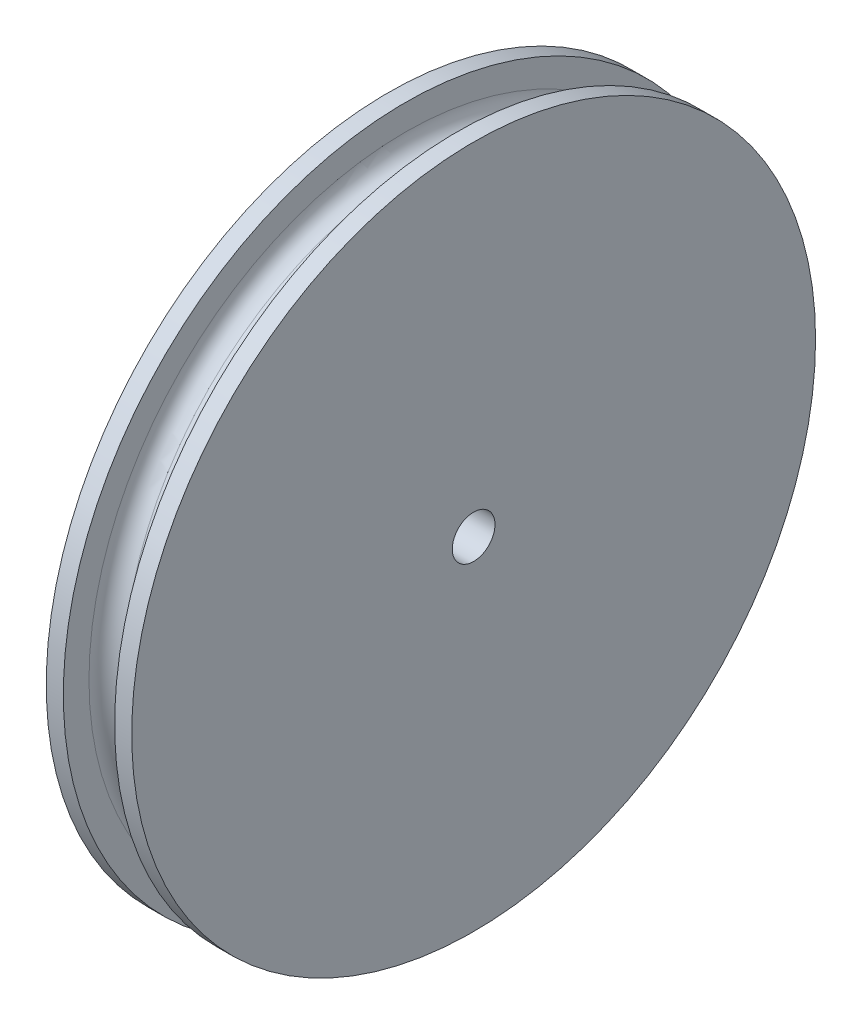
SolidWorks part; units mm, degrees
note: The reader was unsure of these and kept them because the rebuilt part matched: shared geometry of "Sketch1<3>".
ref_plane "Front Plane" through (0, 0, 0) normal (0, 0, 1) x (1, 0, 0)
ref_plane "Top Plane" through (0, 0, 0) normal (0, 1, 0) x (1, 0, 0)
ref_plane "Right Plane" through (0, 0, 0) normal (1, 0, 0) x (0, 0, -1)
sketch "Sketch1" plane through (0, 0, 0) normal (1, 0, 0) x (0, 0, -1)
  circle A0 centre (0, 0) radius 50.8
  circle A1 centre (0, 0) radius 44.45
  circle A2 centre (0, 0) radius 3.175
  dimension "D1" = 6.35
  dimension "D2" = 88.9
  dimension "D3" = 6.35
extrude "Boss-Extrude1" add sketch "Sketch1" along normal mid plane 12.7 contours A0 A2 | A1 A0
extrude "Cut-Extrude1" cut sketch "Sketch1<3>" against normal mid plane 7.62 contours A0 A1
sketch "Sketch1<3>" plane through (0, 0, 0) normal (1, 0, 0) x (0, 0, -1) same geometry as "Sketch1"
fillet "Fillet1" radius 2.54 2 edges at (3.81, 0, -44.45) (-3.81, 0, -44.45)
